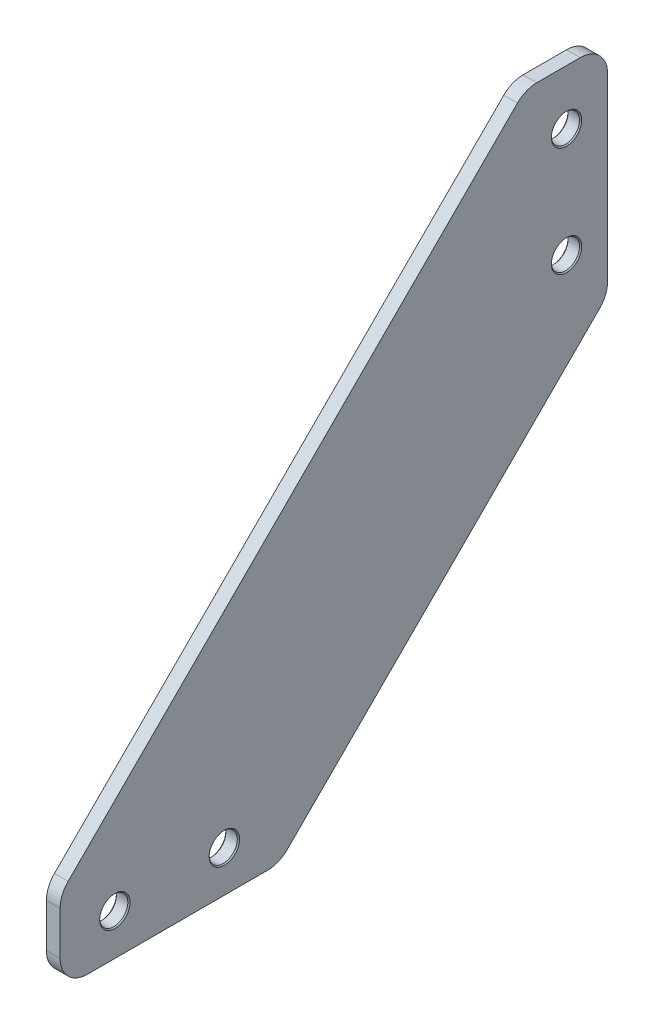
SolidWorks part; units mm, degrees
material "6061 Alloy"
ref_plane "Front Plane" through (0, 0, 0) normal (0, 0, 1) x (1, 0, 0)
ref_plane "Top Plane" through (0, 0, 0) normal (0, 1, 0) x (1, 0, 0)
ref_plane "Right Plane" through (0, 0, 0) normal (1, 0, 0) x (0, 0, -1)
sketch "Sketch1" plane through (0, 0, 0) normal (1, 0, 0) x (0, 0, -1)
  line L0 (0, 0) -> (0, 76.2) construction
  line L1 (0, 127) -> (-19.05, 127)
  line L2 (-19.05, 127) -> (-127, 19.05)
  line L3 (-127, 19.05) -> (-127, 0)
  line L4 (-127, 0) -> (-76.2, 0)
  line L5 (-76.2, 0) -> (0, 0) construction
  line L6 (0, 76.2) -> (0, 127)
  line L7 (-76.2, 0) -> (0, 76.2)
  line L8 (-127, 0) -> (0, 127) construction
  dimension "D1" = 45
  dimension "D2" = 127
  dimension "D3" = 19.05
  dimension "D4" = 50.8
extrude "Boss-Extrude1" add sketch "Sketch1" along normal mid plane 3.175
ref_plane "Plane1" through (0, 9.525, 0) normal (0, -1, 0) x (-1, 0, 0)
ref_plane "Plane2" through (0, 0, 9.525) normal (0, 0, -1) x (-1, 0, 0)
ref_axis "Axis1" through (0, 9.525, 133.35) along (0, 0, -1)
ref_axis "Axis2" through (0, 72.375, 9.525) along (0, 1, 0)
hole_wizard "1/4 Clearance Hole1" positions "Sketch3" profile "Sketch4" hole size "1/4" standard "ANSI Inch" end condition through all
sketch "Sketch3" plane through (1.5875, 0, 0) normal (1, 0, 0) x (0, 0, -1)
  line L0 (-133.35, 9.525) -> (-74.9182, 9.525) construction
  line L1 (-9.525, 72.375) -> (-9.525, 133.35) construction
  line L2 (-127, 19.05) -> (-127, 0) construction
  line L3 (0, 127) -> (-19.05, 127) construction
  point P0 (-114.3, 9.525)
  point P4 (-88.9, 9.525)
  point P6 (-9.525, 88.9)
  point P10 (-9.525, 114.3)
  dimension "D1" = 25.4
  dimension "D2" = 25.4
  dimension "D3" = 12.7
  dimension "D4" = 12.7
sketch "Sketch4" plane through (1.5875, 9.525, 114.3) normal (0, 1, 0) x (0, 0, -1)
  line L0 (0, 0) -> (0, 3.175)
  line L1 (0, 3.175) -> (3.2639, 3.175)
  line L2 (3.2639, 3.175) -> (3.2639, 0)
  line L5 (3.2639, 0) -> (0, 0)
  line L11 (0, -6.35) -> (0, 107.95) construction
  dimension "Thru Hole Dia." = 6.5278
  dimension "Thru Hole Depth" = 3.175
fillet "Fillet1" radius 6.35 6 edges at (0, 76.2, 0) (0, 127, 0) (0, 127, 19.05) (0, 19.05, 127) (0, 0, 76.2) (0, 0, 127)
chamfer "Chamfer1" distance 0.254 angle 45 8 edges at (1.5875, 114.3, 6.2611) (-1.5875, 114.3, 6.2611) (1.5875, 88.9, 6.2611) (-1.5875, 88.9, 6.2611) (1.5875, 9.525, 111.0361) (-1.5875, 9.525, 111.0361) (1.5875, 9.525, 85.6361) (-1.5875, 9.525, 85.6361)
